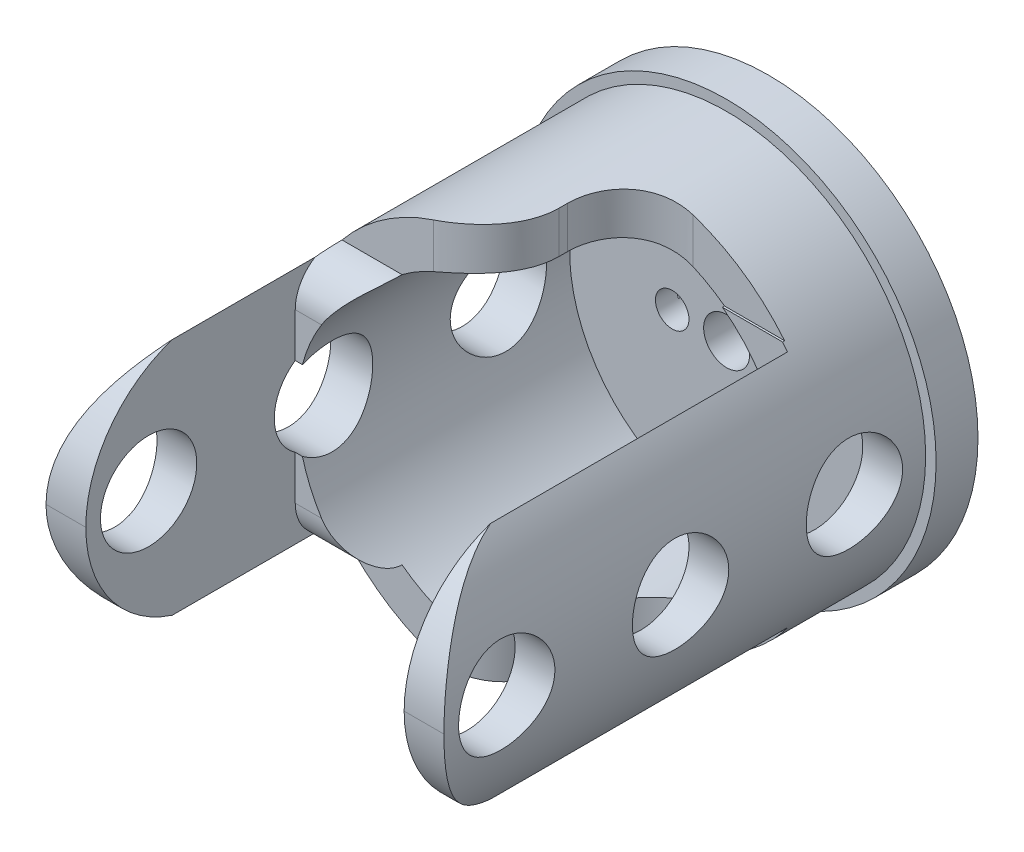
SolidWorks part; units mm, degrees
material "ABS"
ref_plane "Plan de face" through (0, 0, 0) normal (0, 0, 1) x (1, 0, 0)
ref_plane "Plan de dessus" through (0, 0, 0) normal (0, 1, 0) x (1, 0, 0)
ref_plane "Plan de droite" through (0, 0, 0) normal (1, 0, 0) x (0, 0, -1)
sketch "Esquisse1" plane through (0, 0, 0) normal (0, 0, 1) x (1, 0, 0)
  circle A0 centre (0, 0) radius 50
  dimension "D1" = 100
extrude "Boss.-Extru.1" add sketch "Esquisse1" along normal blind 10
sketch "Esquisse2" plane through (0, 0, 0) normal (0, 0, -1) x (-1, 0, 0)
  circle A0 centre (0, 0) radius 47.5
  dimension "D1" = 95
extrude "Enlèv. mat.-Extru.1" cut sketch "Esquisse2" against normal blind 5
sketch "Esquisse6" plane through (0, 0, 10) normal (0, 0, 1) x (1, 0, 0)
  line L0 (0, 0) -> (0, 47.5) construction
  line L1 (0, 47.5) -> (0, -47.5) construction
  line L2 (-22.5, 30) -> (-22.5, -30) construction
  line L3 (-22.5, 30) -> (-36.8273, 30)
  line L4 (-22.5, -30) -> (-36.8273, -30)
  line L5 (22.5, -30) -> (36.8273, -30)
  line L6 (22.5, 30) -> (36.8273, 30)
  circle A0 centre (0, 0) radius 2
  circle A1 centre (0, 0) radius 47.5
  circle A2 centre (0, 0) radius 37.5
  circle A3 centre (0, 0) radius 50 construction
  dimension "D1" = 4
  dimension "D2" = 2.5
  dimension "D3" = 10
  dimension "D4" = 60
extrude "Boss.-Extru.4" add sketch "Esquisse6" along normal blind 115 contours A2 L3 A1 L4 | A2 L5 A1 L6 region at (-38.1648, 0, 10) region at (38.1648, 0, 10)
sketch "Esquisse7" plane through (0, 0, 5) normal (0, 0, -1) x (-1, 0, 0)
  circle A0 centre (0, 0) radius 5.5
  dimension "D1" = 11
extrude "Enlèv. mat.-Extru.2" cut sketch "Esquisse7" against normal blind 100
sketch "Esquisse12" plane through (0, 0, 10) normal (0, 0, 1) x (1, 0, 0)
  line L1 (-3.6437, 25.162) -> (0, 25.162)
  line L2 (-3.6437, 25.162) -> (-3.6437, 15.1247)
  line L3 (-3.6437, 15.1247) -> (0, 15.1247)
  line L4 (0, 25.162) -> (0, 15.1247)
extrude "Boss.-Extru.7" add sketch "Esquisse12" along normal blind 116
sketch "Esquisse14" plane through (0, 0, 0) normal (1, 0, 0) x (0, 0, -1)
  line L0 (-125, 0) -> (-10, 0) construction
  line L1 (-125, 30) -> (-125, -30) construction
  line L2 (-10, 50) -> (-10, -50) construction
  circle A0 centre (-110, 0) radius 11.5
  circle A2 centre (-68.5, 0) radius 11.5
  circle A3 centre (-27, 0) radius 11.5
  dimension "D4" = 23
  dimension "D5" = 23
  dimension "D6" = 23
  dimension "D1" = 100
  dimension "D2" = 17
  dimension "D3" = 41.5
extrude "Enlèv. mat.-Extru.3" cut sketch "Esquisse14" against normal through all both and the other way through all
sketch "Esquisse15" plane through (0, 0, 126) normal (0, 0, 1) x (1, 0, 0)
  line L1 (0, 15.1247) -> (-3.6437, 15.1247)
  line L2 (0, 15.1247) -> (0, 25.162)
  line L3 (0, 25.162) -> (-3.6437, 25.162)
  line L4 (-3.6437, 15.1247) -> (-3.6437, 25.162)
extrude "Enlèv. mat.-Extru.4" cut sketch "Esquisse15" against normal blind 116
sketch "Esquisse16" plane through (0, 0, 5) normal (0, 0, -1) x (-1, 0, 0)
  circle A0 centre (0, 0) radius 20
  circle A1 centre (0, 0) radius 2
  dimension "D1" = 40
extrude "Boss.-Extru.8" add sketch "Esquisse16" along normal blind 16
sketch "Esquisse17" plane through (0, 0, -11) normal (0, 0, -1) x (-1, 0, 0)
  line L0 (0, 0) -> (0, 20) construction
  line L1 (0, 20) -> (0, -20) construction
  line L2 (0, 0) -> (20, 0) construction
  line L3 (20, 0) -> (-20, 0) construction
  line L4 (0, 20) -> (1.98, 14.8687)
  line L5 (0, 20) -> (-1.98, 14.8687)
  line L6 (-0.9649, 14.9689) -> (-3.9011, 19.6158)
  line L7 (-3.9011, 19.6158) -> (-4.8485, 14.1948)
  line L8 (-3.9011, 19.6158) -> (0, 0) construction
  line L9 (0, 0) -> (3.9011, -19.6158) construction
  line L10 (-7.6524, 18.4781) -> (0, 0) construction
  line L11 (-11.1097, 16.6305) -> (0, 0) construction
  line L12 (-14.1402, 14.1441) -> (0, 0) construction
  line L13 (0, 0) -> (-16.6275, 11.1143) construction
  line L14 (0, 0) -> (-18.476, 7.6575) construction
  line L15 (0, 0) -> (-19.6148, 3.9065) construction
  line L16 (-9.9008, 11.2683) -> (-11.1097, 16.6305)
  line L17 (-11.1097, 16.6305) -> (-6.6069, 13.4666)
  line L18 (-11.2656, 9.9039) -> (-16.6275, 11.1143)
  line L19 (-16.6275, 11.1143) -> (-13.4647, 6.6107)
  line L20 (-14.9687, 0.9691) -> (-19.6148, 3.9065)
  line L21 (-19.6148, 3.9065) -> (-14.1934, 4.8524)
  line L22 (-7.6524, 18.4781) -> (-3.8597, 14.4949)
  line L23 (-7.6524, 18.4781) -> (-7.5184, 12.9797)
  line L24 (-14.1402, 14.1441) -> (-9.1121, 11.9151)
  line L25 (-14.1402, 14.1441) -> (-11.9126, 9.1154)
  line L26 (-18.476, 7.6575) -> (-14.4938, 3.8637)
  line L27 (-18.476, 7.6575) -> (-12.9777, 7.522)
  line L28 (-20, 0) -> (-14.8675, 1.9891)
  line L29 (-20, 0) -> (-14.8675, -1.9891)
  line L30 (-14.9687, -0.9691) -> (-19.6148, -3.9065)
  line L31 (-19.6148, -3.9065) -> (-14.1934, -4.8524)
  line L32 (-18.476, -7.6575) -> (-14.4938, -3.8637)
  line L33 (-18.476, -7.6575) -> (-12.9777, -7.522)
  line L34 (-16.6275, -11.1143) -> (-13.4647, -6.6107)
  line L35 (-11.2656, -9.9039) -> (-16.6275, -11.1143)
  line L36 (-14.1402, -14.1441) -> (-11.9126, -9.1154)
  line L37 (-14.1402, -14.1441) -> (-9.1121, -11.9151)
  line L38 (-9.9008, -11.2683) -> (-11.1097, -16.6305)
  line L39 (-11.1097, -16.6305) -> (-6.6069, -13.4666)
  line L40 (-7.6524, -18.4781) -> (-7.5184, -12.9797)
  line L41 (-7.6524, -18.4781) -> (-3.8597, -14.4949)
  line L42 (-3.9011, -19.6158) -> (-4.8485, -14.1948)
  line L43 (-0.9649, -14.9689) -> (-3.9011, -19.6158)
  line L44 (0, -20) -> (-1.98, -14.8687)
  line L45 (0, -20) -> (1.98, -14.8687)
  line L46 (0.9649, -14.9689) -> (3.9011, -19.6158)
  line L47 (3.9011, -19.6158) -> (4.8485, -14.1948)
  line L48 (7.6524, -18.4781) -> (3.8597, -14.4949)
  line L49 (7.6524, -18.4781) -> (7.5184, -12.9797)
  line L50 (11.1097, -16.6305) -> (6.6069, -13.4666)
  line L51 (9.9008, -11.2683) -> (11.1097, -16.6305)
  line L52 (14.1402, -14.1441) -> (9.1121, -11.9151)
  line L53 (14.1402, -14.1441) -> (11.9126, -9.1154)
  line L54 (11.2656, -9.9039) -> (16.6275, -11.1143)
  line L55 (16.6275, -11.1143) -> (13.4647, -6.6107)
  line L56 (18.476, -7.6575) -> (12.9777, -7.522)
  line L57 (18.476, -7.6575) -> (14.4938, -3.8637)
  line L58 (19.6148, -3.9065) -> (14.1934, -4.8524)
  line L59 (14.9687, -0.9691) -> (19.6148, -3.9065)
  line L60 (20, 0) -> (14.8675, -1.9891)
  line L61 (20, 0) -> (14.8675, 1.9891)
  line L62 (14.9687, 0.9691) -> (19.6148, 3.9065)
  line L63 (19.6148, 3.9065) -> (14.1934, 4.8524)
  line L64 (18.476, 7.6575) -> (14.4938, 3.8637)
  line L65 (18.476, 7.6575) -> (12.9777, 7.522)
  line L66 (16.6275, 11.1143) -> (13.4647, 6.6107)
  line L67 (11.2656, 9.9039) -> (16.6275, 11.1143)
  line L68 (14.1402, 14.1441) -> (11.9126, 9.1154)
  line L69 (14.1402, 14.1441) -> (9.1121, 11.9151)
  line L70 (9.9008, 11.2683) -> (11.1097, 16.6305)
  line L71 (11.1097, 16.6305) -> (6.6069, 13.4666)
  line L72 (7.6524, 18.4781) -> (7.5184, 12.9797)
  line L73 (7.6524, 18.4781) -> (3.8597, 14.4949)
  line L74 (3.9011, 19.6158) -> (4.8485, 14.1948)
  line L75 (0.9649, 14.9689) -> (3.9011, 19.6158)
  line L76 (0, 20) -> (1.98, 14.8687)
  circle A0 centre (0, 0) radius 20
  circle A1 centre (0, 0) radius 2
  circle A2 centre (0, 0) radius 15
  circle M45 centre (0, 0) radius 20
  dimension "D4" = 1.98
  dimension "D5" = 3.96
  dimension "D6" = 1.02
  dimension "D8" = 1.02
extrude "Enlèv. mat.-Extru.7" cut sketch "Esquisse17" against normal blind 16 contours L30 L29 M45 | L32 L31 M45 | L34 L33 M45 | L36 L35 M45 | L38 L37 M45 | L40 L39 M45 | L42 L41 M45 | L44 L43 M45 | L46 L45 M45 | L48 L47 M45 | L50 L49 M45 | L52 L51 M45 | L54 L53 M45 | L56 L55 M45 | L58 L57 M45 | L60 L59 M45 | L62 L61 M45 | L64 L63 M45 | L66 L65 M45 | L68 L67 M45 | L70 L69 M45 | L72 L71 M45 | L74 L73 M45 | L4 L75 M45 | L6 L5 M45 | L22 L7 M45 | L23 L17 M45 | L24 L16 M45 | L25 L18 M45 | L27 L19 M45 | L26 L21 M45 | L28 L20 M45 region at (-1.8282, 18.5572, -11) region at (1.8282, 18.5572, -11) region at (-5.4138, 17.8474, -11) region at (5.4138, 17.8474, -11) region at (-8.7896, 16.4494, -11) region at (8.7896, 16.4494, -11) region at (-11.8272, 14.4163, -11) region at (11.8272, 14.4163, -11) region at (-14.413, 11.8311, -11) region at (14.413, 11.8311, -11) region at (-16.447, 8.7941, -11) region at (16.447, 8.7941, -11) region at (-17.8459, 5.4187, -11) region at (17.8459, 5.4187, -11) region at (-18.5577, 1.832, -11) region at (18.5577, 1.832, -11) region at (-18.5577, -1.832, -11) region at (18.5577, -1.832, -11) region at (-17.8459, -5.4187, -11) region at (17.8459, -5.4187, -11) region at (-16.447, -8.7941, -11) region at (16.447, -8.7941, -11) region at (-14.413, -11.8311, -11) region at (14.413, -11.8311, -11) region at (-11.8272, -14.4163, -11) region at (11.8272, -14.4163, -11) region at (-8.7896, -16.4494, -11) region at (8.7896, -16.4494, -11) region at (-5.4138, -17.8474, -11) region at (5.4138, -17.8474, -11) region at (-1.8282, -18.5572, -11) region at (1.8282, -18.5572, -11)
fillet "Congé3" radius 30 4 edges at (29.6636, -30, 125) (-29.6636, -30, 125) (-29.6636, 30, 125) (29.6636, 30, 125)
sketch "Esquisse18" plane through (0, 0, 10) normal (0, 0, 1) x (1, 0, 0)
  line L0 (35, 0) -> (35, 35.7071)
  line L1 (35, 35.7071) -> (35, -35.7071)
  line L2 (35, -15) -> (37, -15)
  line L3 (35, 35.7071) -> (32, 35.7071)
  line L4 (35, 35.7071) -> (35, -35.7071)
  line L5 (35, -35.7071) -> (32, -35.7071)
  line L6 (32, 35.7071) -> (32, -35.7071)
  line L7 (35, 35.7071) -> (37, 35.7071)
  line L8 (35, 35.7071) -> (35, -35.7071)
  line L9 (35, -35.7071) -> (37, -35.7071)
  line L10 (37, 35.7071) -> (37, -35.7071)
  line L11 (35, 0) -> (37, 0)
  line L12 (35, 0) -> (35, 15)
  line L13 (35, 15) -> (37, 15)
  line L14 (37, 0) -> (37, 15)
  line L15 (37, 0) -> (32, 0)
  line L16 (32, 0) -> (34.5, 0)
  line L18 (38, -17) -> (31, -17)
  line L19 (38, -17) -> (38, 17)
  line L20 (38, 17) -> (31, 17)
  line L21 (31, -17) -> (31, 17)
  line L22 (38, -17) -> (31, 17) construction
  line L23 (38, 17) -> (31, -17) construction
  circle A0 centre (0, 0) radius 35
  circle A1 centre (0, 0) radius 50 construction
  arc M17 (22.5, -30) -> (22.5, 30) centre (0, 0) ccw
  dimension "D1" = 70
  dimension "D2" = 3
  dimension "D3" = 2
  dimension "D4" = 15
  dimension "D5" = 2.5
  dimension "D6" = 1
  dimension "D7" = 2
extrude "Enlèv. mat.-Extru.8" cut sketch "Esquisse18" along normal blind 150 contours L19 L20 L10 L18 M17 | L0 L11 L10 M17 | L13 L0 L10 M17 | L10 L20 L8 L13 | L11 L1 L10 M17 | L10 L1 L2 M17 | L18 L10 L2 L1 | L8 L20 L0 M17 | L18 L1 M17 region at (35.8843, -5.3474, 10) region at (35.8843, 5.3474, 10) region at (34.487, 15.8492, 10) region at (36.2519, 12.1846, 10) region at (36.2519, -12.1846, 10) region at (34.487, -15.8492, 10) region at (36, 16, 10) region at (37.5408, 0, 10) region at (36, -16, 10)
sketch "Esquisse21" plane through (38, 0, 0) normal (-1, 0, 0) x (0, 0, 1)
  line L0 (68.5, 0) -> (33.5, 0) construction
  line L1 (95, 30) -> (10, 30) construction
  line L2 (33.5, 30) -> (125, 30)
  line L3 (33.5, 30) -> (33.5, 0)
  line L4 (33.5, 0) -> (125, 0)
  line L5 (125, 30) -> (125, 0)
  line L7 (33.5, 0) -> (95, 0)
  line L8 (33.5, 0) -> (33.5, -30)
  line L9 (33.5, -30) -> (95, -30)
  line L10 (95, 0) -> (95, -30)
  line L11 (95, 0) -> (125, 0)
  line L12 (95, 0) -> (95, -30)
  line L13 (95, -30) -> (125, -30)
  line L14 (125, 0) -> (125, -30)
  line M2 (119.7184, 17) -> (10, 17)
  line M4 (10, -17) -> (119.7184, -17)
  arc M5 (119.7184, -17) -> (125, 0) centre (95, 0) ccw
  arc M6 (125, 0) -> (119.7184, 17) centre (95, 0) ccw
  circle M7 centre (110, 0) radius 11.5
  circle M8 centre (68.5, 0) radius 11.5
  circle M9 centre (27, 0) radius 11.5
  dimension "D1" = 35
extrude "Enlèv. mat.-Extru.9" cut sketch "Esquisse21" along normal blind 20 contours L5 L2 L3 M2 M6 | L4 L3 M9 M8 M7 M6 M2 | L10 L4 L8 M8 M9 M4 | L4 L10 M4 M5 M7 | L10 L8 L9 M4 | L14 L10 L13 M5 M4 region at (38, 23.2478, 80.2943) region at (38, 9.9281, 75.5662) region at (38, -8.7985, 123.3199) region at (38, -22.7664, 110.9241) region at (38, -0.6381, 47.75) region at (38, -23.5, 64.25)
ref_plane "Plan2" through (-37.5, 0, 125) normal (-1, 0, 0) x (0, 0, 1)
sketch "Esquisse27" plane through (-37.5, 0, 125) normal (-1, 0, 0) x (0, 0, 1)
  line L1 (0, 0) -> (-50, 0)
  line L2 (0, 0) -> (0, 30)
  line L3 (0, 30) -> (-50, 30)
  line L4 (-50, 0) -> (-50, 30)
  line L5 (0, 0) -> (-50, 0)
  line L6 (0, 0) -> (0, -30)
  line L7 (0, -30) -> (-50, -30)
  line L8 (-50, 0) -> (-50, -30)
  dimension "D1" = 50
  dimension "D2" = 30
  dimension "D3" = 30
extrude "Enlèv. mat.-Extru.10" cut sketch "Esquisse27" against normal blind 20 and the other way blind 0.5 contours L1 L8 L7 L6 | L4 L1 L2 L3 region at (-37.5, -15, 100) region at (-37.5, 15, 100)
fillet "Congé5" radius 10 2 edges at (-29.6636, 30, 75) (-29.6636, -30, 75)
sketch "Esquisse28" plane through (0, 0, 10) normal (0, 0, 1) x (1, 0, 0)
  line L0 (-36.8273, 30) -> (-22.5, 30)
  line L1 (22.5, 30) -> (36.8273, 30)
  line L2 (-36.8273, -30) -> (-22.5, -30)
  line L3 (22.5, -30) -> (36.8273, -30)
  circle A0 centre (0, 0) radius 47.5
  circle A1 centre (0, 0) radius 37.5
  line M5 (22.5, 30) -> (36.8273, 30)
  line M7 (36.8273, -30) -> (22.5, -30)
  line M13 (-22.5, -30) -> (-36.8273, -30)
  line M15 (-36.8273, 30) -> (-22.5, 30)
  dimension "D1" = 95
extrude "Boss.-Extru.13" add sketch "Esquisse28" along normal blind 23 contours A1 A0 M5 M15 | A1 A0 M13 M7 region at (0, 38.5359, 10) region at (0, -38.5359, 10)
sketch "Esquisse29" plane through (0, 0, 33) normal (0, 0, 1) x (1, 0, 0)
  line L0 (0, 47.5) -> (0, 37.5)
  line L1 (0, 37.5) -> (0, -37.5)
  line L2 (0, -37.5) -> (0, -47.5)
  line L3 (-36.8273, 30) -> (-22.5, 30)
  line L4 (-36.8273, -30) -> (-22.5, -30)
  arc A0 (36.8273, 30) -> (-36.8273, 30) centre (0, 0) ccw construction
  arc A1 (22.5, 30) -> (-22.5, 30) centre (0, 0) ccw construction
  arc A2 (-22.5, -30) -> (22.5, -30) centre (0, 0) ccw construction
  arc A3 (-36.8273, -30) -> (36.8273, -30) centre (0, 0) ccw construction
  arc A4 (33.4253, 17) -> (33.4253, -17) centre (0, 0) ccw construction
  arc A5 (-31.7214, -20) -> (-22.5, -30) centre (0, 0) ccw construction
  circle A6 centre (0, 0) radius 37.5
  circle A7 centre (0, 0) radius 47.5
  arc M2 (-22.5, 30) -> (22.5, 30) centre (0, 0) cw
  arc M4 (36.8273, 30) -> (-36.8273, 30) centre (0, 0) ccw
  line M5 (-36.8273, 30) -> (-22.5, 30)
extrude "Boss.-Extru.15" add sketch "Esquisse29" along normal blind 32 contours L4 A7 L2 A6 | L0 M4 M5 M2 region at (-16.1789, 38.5359, 33) region at (-16.1789, -38.5359, 33)
fillet "Congé6" radius 15 1 edges at (0, -42.5, 33)
fillet "Congé7" radius 15 1 edges at (0, -42.5, 65)
fillet "Congé8" radius 15 1 edges at (0, 42.5, 65)
fillet "Congé9" radius 15 1 edges at (0, 42.5, 33)
sketch "Esquisse30" plane through (0, 0, 5) normal (0, 0, 1) x (1, 0, 0)
  circle A0 centre (0, 0) radius 5.5
  point P3 (0, 0)
extrude "Enlèv. mat.-Extru.11" cut sketch "Esquisse30" against normal blind 40
sketch "Esquisse31" plane through (0, 0, -11) normal (0, 0, -1) x (-1, 0, 0)
  circle A0 centre (-13, 0) radius 2.5
  circle A1 centre (13, 0) radius 2.5
  dimension "D1" = 5
  dimension "D2" = 5
  dimension "D3" = 13
  dimension "D4" = 13
extrude "Enlèv. mat.-Extru.12" cut sketch "Esquisse31" against normal blind 40
sketch "Esquisse32" plane through (0, 0, 10) normal (0, 0, 1) x (1, 0, 0)
  circle A0 centre (-13, 0) radius 4
  circle A1 centre (13, 0) radius 4
  dimension "D1" = 8
  dimension "D2" = 8
extrude "Enlèv. mat.-Extru.13" cut sketch "Esquisse32" against normal blind 11
